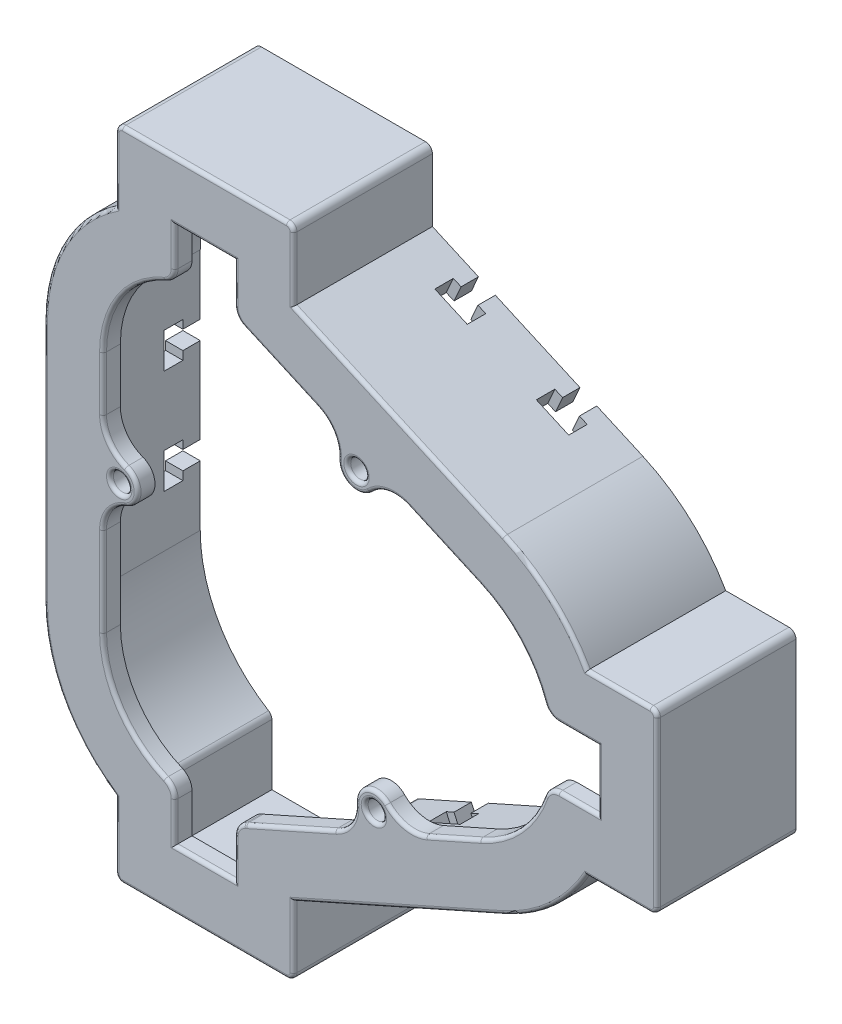
SolidWorks part; units mm, degrees
ref_plane "Front Plane" through (0, 0, 0) normal (0, 0, 1) x (1, 0, 0)
ref_plane "Top Plane" through (0, 0, 0) normal (0, 1, 0) x (1, 0, 0)
ref_plane "Right Plane" through (0, 0, 0) normal (1, 0, 0) x (0, 0, -1)
sketch "Sketch1" plane through (0, 0, -80.01) normal (0, 0, -1) x (-1, 0, 0)
  line L0 (14.1705, 137.7093) -> (22.108, 137.7093) construction
  line L1 (-128.3273, 40.8549) -> (-128.3273, 32.9174) construction
  line L2 (14.1705, -63.937) -> (22.108, -63.937) construction
  line L3 (55.2868, -7.5638) -> (55.2868, 81.3362)
  line L4 (29.093, 120.8247) -> (29.093, 135.1693)
  line L5 (29.093, 135.1693) -> (22.108, 135.1693)
  line L6 (14.1705, 135.1693) -> (22.108, 135.1693)
  line L7 (14.1705, 135.1693) -> (7.1855, 135.1693)
  line L8 (7.1855, 135.1693) -> (7.1855, 120.8247)
  line L9 (3.0278, 115.2711) -> (-82.5915, 77.144)
  line L10 (-111.5749, 47.8399) -> (-125.7873, 47.8399)
  line L11 (-125.7873, 47.8399) -> (-125.7873, 40.8549)
  line L12 (-125.7873, 40.8549) -> (-125.7873, 32.9174)
  line L13 (-125.7873, 32.9174) -> (-125.7873, 25.9324)
  line L14 (-125.7873, 25.9324) -> (-111.5749, 25.9324)
  line L15 (-82.5915, -3.3716) -> (3.0278, -41.4987)
  line L16 (7.1855, -47.0524) -> (7.1855, -61.397)
  line L17 (7.1855, -61.397) -> (14.1705, -61.397)
  line L18 (14.1705, -61.397) -> (22.108, -61.397)
  line L19 (22.108, -61.397) -> (29.093, -61.397)
  line L20 (29.093, -61.397) -> (29.093, -47.0524)
  line L21 (57.8268, -7.5638) -> (57.8268, 81.3362)
  line L22 (31.633, 120.8247) -> (31.633, 137.7093)
  line L23 (31.633, 137.7093) -> (22.108, 137.7093)
  line L24 (22.108, 137.7093) -> (22.108, 117.6323)
  line L25 (14.1705, 117.6323) -> (14.1705, 137.7093)
  line L26 (14.1705, 137.7093) -> (4.6455, 137.7093)
  line L27 (4.6455, 137.7093) -> (4.6455, 120.8247)
  line L28 (1.9945, 117.5914) -> (-83.6248, 79.4643)
  line L29 (-111.5749, 50.3799) -> (-128.3273, 50.3799)
  line L30 (-128.3273, 50.3799) -> (-128.3273, 40.8549)
  line L31 (-128.3273, 40.8549) -> (-106.0032, 40.8549)
  line L32 (-106.0032, 32.9174) -> (-128.3273, 32.9174)
  line L33 (-128.3273, 32.9174) -> (-128.3273, 23.3924)
  line L34 (-128.3273, 23.3924) -> (-111.5749, 23.3924)
  line L35 (-83.6248, -5.692) -> (1.9945, -43.8191)
  line L36 (4.6455, -47.0524) -> (4.6455, -63.937)
  line L37 (4.6455, -63.937) -> (14.1705, -63.937)
  line L38 (14.1705, -63.937) -> (14.1705, -43.86)
  line L39 (22.108, -43.86) -> (22.108, -63.937)
  line L40 (22.108, -63.937) -> (31.633, -63.937)
  line L41 (31.633, -63.937) -> (31.633, -47.0524)
  line L42 (57.8268, -7.5638) -> (57.8268, 81.3362) construction
  line L43 (31.633, 120.8247) -> (31.633, 137.7093) construction
  line L44 (31.633, 137.7093) -> (22.108, 137.7093) construction
  line L47 (14.1705, 137.7093) -> (4.6455, 137.7093) construction
  line L48 (4.6455, 137.7093) -> (4.6455, 120.8247) construction
  line L49 (1.9945, 117.5914) -> (-83.6248, 79.4643) construction
  line L50 (-111.5749, 50.3799) -> (-128.3273, 50.3799) construction
  line L51 (-128.3273, 50.3799) -> (-128.3273, 40.8549) construction
  line L54 (-128.3273, 32.9174) -> (-128.3273, 23.3924) construction
  line L55 (-128.3273, 23.3924) -> (-111.5749, 23.3924) construction
  line L56 (-83.6248, -5.692) -> (1.9945, -43.8191) construction
  line L57 (4.6455, -47.0524) -> (4.6455, -63.937) construction
  line L58 (4.6455, -63.937) -> (14.1705, -63.937) construction
  line L61 (22.108, -63.937) -> (31.633, -63.937) construction
  line L62 (31.633, -63.937) -> (31.633, -47.0524) construction
  line L63 (76.8768, -7.5638) -> (76.8768, 81.3362)
  line L64 (50.683, 130.234) -> (50.683, 156.7593)
  line L65 (50.683, 156.7593) -> (22.108, 156.7593)
  line L66 (14.1705, 156.7593) -> (22.108, 156.7593)
  line L67 (14.1705, 156.7593) -> (-14.4045, 156.7593)
  line L68 (-14.4045, 156.7593) -> (-14.4045, 131.1423)
  line L69 (-14.4045, 131.1423) -> (-91.3743, 96.8669)
  line L70 (-121.6907, 69.4299) -> (-147.3773, 69.4299)
  line L71 (-147.3773, 69.4299) -> (-147.3773, 40.8549)
  line L72 (-147.3773, 40.8549) -> (-147.3773, 32.9174)
  line L73 (-147.3773, 32.9174) -> (-147.3773, 4.3424)
  line L74 (-147.3773, 4.3424) -> (-121.6907, 4.3424)
  line L75 (-91.3743, -23.0945) -> (-14.4045, -57.3699)
  line L76 (-14.4045, -57.3699) -> (-14.4045, -82.987)
  line L77 (-14.4045, -82.987) -> (14.1705, -82.987)
  line L78 (14.1705, -82.987) -> (22.108, -82.987)
  line L79 (22.108, -82.987) -> (50.683, -82.987)
  line L80 (50.683, -82.987) -> (50.683, -56.4617)
  line L81 (70.5268, -7.5638) -> (70.5268, 81.3362)
  line L82 (44.333, 126.7051) -> (44.333, 150.4093)
  line L83 (44.333, 150.4093) -> (22.108, 150.4093)
  line L84 (14.1705, 150.4093) -> (22.108, 150.4093)
  line L85 (14.1705, 150.4093) -> (-8.0545, 150.4093)
  line L86 (-8.0545, 150.4093) -> (-8.0545, 127.0188)
  line L87 (-8.0545, 127.0188) -> (-88.7911, 91.066)
  line L88 (-117.8756, 63.0799) -> (-141.0273, 63.0799)
  line L89 (-141.0273, 63.0799) -> (-141.0273, 40.8549)
  line L90 (-141.0273, 40.8549) -> (-141.0273, 32.9174)
  line L91 (-141.0273, 32.9174) -> (-141.0273, 10.6924)
  line L92 (-141.0273, 10.6924) -> (-117.8756, 10.6924)
  line L93 (-88.7911, -17.2937) -> (-8.0545, -53.2465)
  line L94 (-8.0545, -53.2465) -> (-8.0545, -76.637)
  line L95 (-8.0545, -76.637) -> (14.1705, -76.637)
  line L96 (14.1705, -76.637) -> (22.108, -76.637)
  line L97 (22.108, -76.637) -> (44.333, -76.637)
  line L98 (44.333, -76.637) -> (44.333, -52.9327)
  circle A0 centre (18.1393, 81.3362) radius 19.05 construction
  circle A1 centre (18.1393, -7.5638) radius 47.625 construction
  circle A2 centre (-58.3701, 37.7264) radius 19.05 construction
  circle A3 centre (18.1393, 81.3362) radius 19.05 construction
  circle A4 centre (18.1393, -7.5638) radius 47.625 construction
  circle A5 centre (-58.3701, 37.7264) radius 19.05 construction
  arc A6 (-63.9876, 68.0881) -> (-52.7526, 7.3647) centre (-58.3701, 37.7264) ccw construction
  arc A7 (-63.9876, 68.0881) -> (-52.7526, 7.3647) centre (-58.3701, 37.7264) ccw construction
  arc A8 (-52.5707, 6.3814) -> (-64.1696, 69.0714) centre (-58.3701, 37.7264) ccw construction
  arc A9 (-52.5707, 6.3814) -> (-64.1696, 69.0714) centre (-58.3701, 37.7264) ccw construction
  circle A10 centre (18.1393, 81.3362) radius 36.5125 construction
  circle A11 centre (18.1393, 81.3362) radius 36.5125 construction
  circle A12 centre (49.3813, 43.2476) radius 3.3782
  circle A13 centre (-43.805, -14.1791) radius 3.3782
  circle A14 centre (-37.4305, 90.7903) radius 3.3782
  arc A15 (33.5733, -44.1273) -> (57.8268, -7.5638) centre (18.1393, -7.5638) ccw
  arc A16 (57.8268, 81.3362) -> (33.5733, 117.8997) centre (18.1393, 81.3362) ccw
  arc A17 (31.633, 120.8247) -> (33.5733, 117.8997) centre (34.808, 120.8247) ccw
  arc A18 (14.1705, 117.6323) -> (22.108, 117.6323) centre (18.1393, 81.3362) ccw
  arc A19 (2.7053, 117.8997) -> (4.6455, 120.8247) centre (1.4705, 120.8247) ccw
  arc A20 (2.7053, 117.8997) -> (1.9945, 117.5914) centre (18.1393, 81.3362) ccw
  arc A21 (-83.6248, 79.4643) -> (-108.5831, 52.4919) centre (-64.6643, 36.8862) ccw
  arc A22 (-111.5749, 50.3799) -> (-108.5831, 52.4919) centre (-111.5749, 53.5549) ccw
  arc A23 (-106.0032, 32.9174) -> (-106.0032, 40.8549) centre (-64.6643, 36.8862) ccw
  arc A24 (-108.5831, 21.2805) -> (-111.5749, 23.3924) centre (-111.5749, 20.2174) ccw
  arc A25 (-108.5831, 21.2805) -> (-83.6248, -5.692) centre (-64.6643, 36.8862) ccw
  arc A26 (1.9945, -43.8191) -> (2.7053, -44.1273) centre (18.1393, -7.5638) ccw
  arc A27 (4.6455, -47.0524) -> (2.7053, -44.1273) centre (1.4705, -47.0524) ccw
  arc A28 (22.108, -43.86) -> (14.1705, -43.86) centre (18.1393, -7.5638) ccw
  arc A29 (33.5733, -44.1273) -> (31.633, -47.0524) centre (34.808, -47.0524) ccw
  arc A30 (33.5733, -44.1273) -> (57.8268, -7.5638) centre (18.1393, -7.5638) ccw construction
  arc A31 (57.8268, 81.3362) -> (33.5733, 117.8997) centre (18.1393, 81.3362) ccw construction
  arc A32 (31.633, 120.8247) -> (33.5733, 117.8997) centre (34.808, 120.8247) ccw construction
  arc A34 (2.7053, 117.8997) -> (4.6455, 120.8247) centre (1.4705, 120.8247) ccw construction
  arc A35 (2.7053, 117.8997) -> (1.9945, 117.5914) centre (18.1393, 81.3362) ccw construction
  arc A36 (-83.6248, 79.4643) -> (-108.5831, 52.4919) centre (-64.6643, 36.8862) ccw construction
  arc A37 (-111.5749, 50.3799) -> (-108.5831, 52.4919) centre (-111.5749, 53.5549) ccw construction
  arc A39 (-108.5831, 21.2805) -> (-111.5749, 23.3924) centre (-111.5749, 20.2174) ccw construction
  arc A40 (-108.5831, 21.2805) -> (-83.6248, -5.692) centre (-64.6643, 36.8862) ccw construction
  arc A41 (1.9945, -43.8191) -> (2.7053, -44.1273) centre (18.1393, -7.5638) ccw construction
  arc A42 (4.6455, -47.0524) -> (2.7053, -44.1273) centre (1.4705, -47.0524) ccw construction
  arc A44 (33.5733, -44.1273) -> (31.633, -47.0524) centre (34.808, -47.0524) ccw construction
  arc A45 (-23.9136, 44.8884) -> (-23.2414, 39.853) centre (-64.6643, 36.8862) ccw construction
  arc A46 (-23.9136, 44.8884) -> (-23.2414, 39.853) centre (-64.6643, 36.8862) ccw construction
  circle A47 centre (-43.805, -14.1791) radius 6.7564
  circle A48 centre (49.3813, 43.2476) radius 6.7564
  circle A49 centre (-37.4305, 90.7903) radius 6.7564
  arc A50 (32.5855, -41.7872) -> (55.2868, -7.5638) centre (18.1393, -7.5638) ccw
  arc A51 (55.2868, 81.3362) -> (32.5855, 115.5596) centre (18.1393, 81.3362) ccw
  arc A52 (29.093, 120.8247) -> (32.5855, 115.5596) centre (34.808, 120.8247) ccw
  arc A53 (3.693, 115.5596) -> (7.1855, 120.8247) centre (1.4705, 120.8247) ccw
  arc A54 (3.693, 115.5596) -> (3.0278, 115.2711) centre (18.1393, 81.3362) ccw
  arc A55 (-82.5915, 77.144) -> (-106.1897, 51.6414) centre (-64.6643, 36.8862) ccw
  arc A56 (-111.5749, 47.8399) -> (-106.1897, 51.6414) centre (-111.5749, 53.5549) ccw
  arc A57 (-106.1897, 22.1309) -> (-111.5749, 25.9324) centre (-111.5749, 20.2174) ccw
  arc A58 (-106.1897, 22.1309) -> (-82.5915, -3.3716) centre (-64.6643, 36.8862) ccw
  arc A59 (3.0278, -41.4987) -> (3.693, -41.7872) centre (18.1393, -7.5638) ccw
  arc A60 (7.1855, -47.0524) -> (3.693, -41.7872) centre (1.4705, -47.0524) ccw
  arc A61 (32.5855, -41.7872) -> (29.093, -47.0524) centre (34.808, -47.0524) ccw
  arc A62 (50.683, -56.4617) -> (76.8768, -7.5638) centre (18.1393, -7.5638) ccw
  arc A63 (76.8768, 81.3362) -> (50.683, 130.234) centre (18.1393, 81.3362) ccw
  arc A64 (50.683, 130.234) -> (50.683, 130.234) centre (50.683, 130.234) ccw
  arc A65 (-14.4045, 131.1423) -> (-14.4045, 131.1423) centre (-14.4045, 131.1423) ccw
  arc A66 (-14.4045, 131.1423) -> (-14.4045, 131.1423) centre (-14.4045, 131.1423) cw
  arc A67 (-91.3743, 96.8669) -> (-121.6907, 69.4299) centre (-64.6643, 36.8862) ccw
  arc A68 (-121.6907, 69.4299) -> (-121.6907, 69.4299) centre (-121.6907, 69.4299) ccw
  arc A69 (-121.6907, 4.3424) -> (-121.6907, 4.3424) centre (-121.6907, 4.3424) ccw
  arc A70 (-121.6907, 4.3424) -> (-91.3743, -23.0945) centre (-64.6643, 36.8862) ccw
  arc A71 (-14.4045, -57.3699) -> (-14.4045, -57.3699) centre (-14.4045, -57.3699) cw
  arc A72 (-14.4045, -57.3699) -> (-14.4045, -57.3699) centre (-14.4045, -57.3699) ccw
  arc A73 (50.683, -56.4617) -> (50.683, -56.4617) centre (50.683, -56.4617) ccw
  arc A74 (44.333, -52.9327) -> (70.5268, -7.5638) centre (18.1393, -7.5638) ccw
  arc A75 (70.5268, 81.3362) -> (44.333, 126.7051) centre (18.1393, 81.3362) ccw
  arc A76 (44.333, 126.7051) -> (44.333, 126.7051) centre (44.333, 126.7051) ccw
  arc A77 (-8.0545, 127.0188) -> (-8.0545, 127.0188) centre (-8.0545, 127.0188) ccw
  arc A78 (-8.0545, 127.0188) -> (-8.0545, 127.0188) centre (-8.0545, 127.0188) cw
  arc A79 (-88.7911, 91.066) -> (-117.8756, 63.0799) centre (-64.6643, 36.8862) ccw
  arc A80 (-117.8756, 63.0799) -> (-117.8756, 63.0799) centre (-117.8756, 63.0799) ccw
  arc A81 (-117.8756, 10.6924) -> (-117.8756, 10.6924) centre (-117.8756, 10.6924) ccw
  arc A82 (-117.8756, 10.6924) -> (-88.7911, -17.2937) centre (-64.6643, 36.8862) ccw
  arc A83 (-8.0545, -53.2465) -> (-8.0545, -53.2465) centre (-8.0545, -53.2465) cw
  arc A84 (-8.0545, -53.2465) -> (-8.0545, -53.2465) centre (-8.0545, -53.2465) ccw
  arc A85 (44.333, -52.9327) -> (44.333, -52.9327) centre (44.333, -52.9327) ccw
  point P68 (-40.8151, 98.5279)
  arc M83 (33.5733, -44.1273) -> (57.8268, -7.5638) centre (18.1393, -7.5638) ccw
  line M84 (57.8268, -7.5638) -> (57.8268, 81.3362)
  arc M85 (57.8268, 81.3362) -> (33.5733, 117.8997) centre (18.1393, 81.3362) ccw
  arc M86 (33.5733, 117.8997) -> (31.633, 120.8247) centre (34.808, 120.8247) cw
  line M87 (31.633, 120.8247) -> (31.633, 137.7093)
  line M88 (31.633, 137.7093) -> (22.108, 137.7093)
  line M89 (22.108, 137.7093) -> (22.108, 117.6323)
  line M91 (14.1705, 117.6323) -> (14.1705, 137.7093)
  line M92 (14.1705, 137.7093) -> (4.6455, 137.7093)
  line M93 (4.6455, 137.7093) -> (4.6455, 120.8247)
  arc M94 (4.6455, 120.8247) -> (2.7053, 117.8997) centre (1.4705, 120.8247) cw
  arc M95 (2.7053, 117.8997) -> (1.9945, 117.5914) centre (18.1393, 81.3362) ccw
  line M96 (1.9945, 117.5914) -> (-83.6248, 79.4643)
  arc M97 (-83.6248, 79.4643) -> (-108.5831, 52.4919) centre (-64.6643, 36.8862) ccw
  arc M98 (-108.5831, 52.4919) -> (-111.5749, 50.3799) centre (-111.5749, 53.5549) cw
  line M99 (-111.5749, 50.3799) -> (-128.3273, 50.3799)
  line M100 (-128.3273, 50.3799) -> (-128.3273, 40.8549)
  line M101 (-128.3273, 40.8549) -> (-106.0032, 40.8549)
  line M103 (-106.0032, 32.9174) -> (-128.3273, 32.9174)
  line M104 (-128.3273, 32.9174) -> (-128.3273, 23.3924)
  line M105 (-128.3273, 23.3924) -> (-111.5749, 23.3924)
  arc M106 (-111.5749, 23.3924) -> (-108.5831, 21.2805) centre (-111.5749, 20.2174) cw
  arc M107 (-108.5831, 21.2805) -> (-83.6248, -5.692) centre (-64.6643, 36.8862) ccw
  line M108 (-83.6248, -5.692) -> (1.9945, -43.8191)
  arc M109 (1.9945, -43.8191) -> (2.7053, -44.1273) centre (18.1393, -7.5638) ccw
  arc M110 (2.7053, -44.1273) -> (4.6455, -47.0524) centre (1.4705, -47.0524) cw
  line M111 (4.6455, -47.0524) -> (4.6455, -63.937)
  line M112 (4.6455, -63.937) -> (14.1705, -63.937)
  line M113 (14.1705, -63.937) -> (14.1705, -43.86)
  line M115 (22.108, -43.86) -> (22.108, -63.937)
  line M116 (22.108, -63.937) -> (31.633, -63.937)
  line M117 (31.633, -63.937) -> (31.633, -47.0524)
  arc M118 (31.633, -47.0524) -> (33.5733, -44.1273) centre (34.808, -47.0524) cw
  dimension "D2" = 6.7564
  dimension "D3" = 8.4455
  dimension "D4" = 8.4455
  dimension "D5" = 8.4455
  dimension "D6" = 3.3782
  dimension "D1" = 0
  dimension "D7" = 2.54
  dimension "D8" = 19.05
  dimension "D9" = 12.7
extrude "Boss-Extrude1" add sketch "Sketch1" along normal blind 6.35 contours L3 A48 A12 | L9 A49 A14 | L15 A47 A13 | L92 A82 L93 L94 L95 L96 L97 L98 A74 L81 A75 L82 L83 L84 L85 L86 L87 A79 L88 L89 L90 L91 L18 L12 L6 M113 M112 M111 M110 M109 M108 M107 M106 M105 M104 M103 M101 M100 M99 M98 M97 M96 M95 M94 M93 M92 M91 M89 M88 M87 | L16 A60 A59 L15 A47 A58 A57 L14 L13 L17 M103 M104 M105 M106 M107 M108 M109 M110 M111 M112 M113 | A50 A61 L20 L19 L5 L4 A52 A51 L3 A48 M115 M116 M117 M118 M83 M84 M85 M86 M87 M88 M89 | L10 A56 A55 L9 A49 A54 A53 L8 L7 L11 M91 M92 M93 M94 M95 M96 M97 M98 M99 M100 M101 | L74 A70 L75 L76 L77 L78 L79 L80 A62 L63 A63 L64 L65 L66 L67 L68 L69 A67 L70 L71 L72 L73 A82 L92 L91 L90 L89 L88 A79 L87 L86 L85 L84 L83 L82 A75 L81 A74 L98 L97 L96 L95 L94 L93 | L3 A48 | L9 A49 | L15 A47 region at (-57.3347, 16.2007, -80.01) region at (-42.8101, 43.2476, -80.01) region at (-55.6291, 43.2476, -80.01) region at (-12.4476, -62.667, -80.01) region at (-10.678, 136.8923, -80.01) region at (46.3466, -19.8865, -80.01) region at (46.1297, -19.3994, -80.01) region at (32.5874, 95.2231, -80.01) region at (39.972, 96.4976, -80.01) region at (-67.0221, -33.7495, -80.01) region at (-60.8207, -32.2059, -80.01)
extrude "Boss-Extrude2" add sketch "Sketch1<3>" along normal blind 50.8 contours L74 A70 L75 L76 L77 L78 L79 L80 A62 L63 A63 L64 L65 L66 L67 L68 L69 A67 L70 L71 L72 L73 A82 L92 L91 L90 L89 L88 A79 L87 L86 L85 L84 L83 L82 A75 L81 A74 L98 L97 L96 L95 L94 L93 region at (-67.0221, -33.7495, -80.01)
sketch "Sketch1<3>" plane through (0, 0, -80.01) normal (0, 0, -1) x (-1, 0, 0) same geometry as "Sketch1"
sketch "Sketch2" plane through (-76.8768, 0, 0) normal (-1, 0, 0) x (0, 0, 1)
  line L0 (-80.01, 36.8862) -> (-130.81, 36.8862) construction
  line L1 (-130.81, 395.458) -> (-130.81, 402.2144)
  line L2 (-80.01, -7.5638) -> (-80.01, 81.3362) construction
  line L3 (-130.81, -7.5638) -> (-130.81, 81.3362) construction
  line L4 (-130.81, 52.558) -> (-124.46, 52.558)
  line L5 (-124.46, 52.558) -> (-124.46, 49.4592)
  line L6 (-124.46, 49.4592) -> (-117.602, 49.4592)
  line L7 (-117.602, 49.4592) -> (-117.602, 62.4132)
  line L8 (-117.602, 55.9362) -> (-130.81, 55.9362) construction
  line L9 (-124.46, 62.4132) -> (-117.602, 62.4132)
  line L10 (-130.81, 59.3144) -> (-124.46, 59.3144)
  line L11 (-124.46, 59.3144) -> (-124.46, 62.4132)
  line L12 (-130.81, 14.458) -> (-124.46, 14.458)
  line L13 (-124.46, 14.458) -> (-124.46, 11.3592)
  line L14 (-124.46, 11.3592) -> (-117.602, 11.3592)
  line L15 (-117.602, 24.3132) -> (-117.602, 11.3592)
  line L16 (-124.46, 24.3132) -> (-117.602, 24.3132)
  line L17 (-124.46, 21.2144) -> (-124.46, 24.3132)
  line L18 (-130.81, 21.2144) -> (-124.46, 21.2144)
  line L19 (-130.81, 14.458) -> (-130.81, 21.2144)
  line L20 (-130.81, 52.558) -> (-130.81, 59.3144)
  line L21 (-130.81, 402.2144) -> (-124.46, 402.2144)
  line L22 (-124.46, 402.2144) -> (-124.46, 405.3132)
  line L23 (-124.46, 405.3132) -> (-117.602, 405.3132)
  line L24 (-117.602, 405.3132) -> (-117.602, 392.3592)
  line L25 (-124.46, 392.3592) -> (-117.602, 392.3592)
  line L26 (-124.46, 395.458) -> (-124.46, 392.3592)
  line L27 (-130.81, 395.458) -> (-124.46, 395.458)
  line L28 (-130.81, 433.558) -> (-130.81, 440.3144)
  line L29 (-130.81, 440.3144) -> (-124.46, 440.3144)
  line L30 (-124.46, 440.3144) -> (-124.46, 443.4132)
  line L31 (-124.46, 443.4132) -> (-117.602, 443.4132)
  line L32 (-117.602, 430.4592) -> (-117.602, 443.4132)
  line L33 (-124.46, 430.4592) -> (-117.602, 430.4592)
  line L34 (-124.46, 433.558) -> (-124.46, 430.4592)
  line L35 (-130.81, 433.558) -> (-124.46, 433.558)
  dimension "D1" = 6.858
  dimension "D2" = 6.7564
  dimension "D3" = 6.35
  dimension "D4" = 19.05
  dimension "D6" = 6.477
  dimension "D5" = 2
sketch "Sketch3" plane through (51.1185, 114.7931, 0) normal (0.4068, 0.9135, 0) x (0.9135, -0.4068, 0)
  line L0 (1.9385, 130.81) -> (1.9385, 80.01) construction
  line L1 (-40.1897, 130.81) -> (44.0668, 130.81) construction
  line L2 (-40.1897, 80.01) -> (44.0668, 80.01) construction
  line L3 (22.2585, 130.81) -> (22.2585, 117.7036) construction
  line L4 (18.8803, 130.81) -> (18.8803, 124.46)
  line L5 (18.8803, 124.46) -> (15.7815, 124.46)
  line L6 (15.7815, 124.46) -> (15.7815, 117.7036)
  line L7 (15.7815, 117.7036) -> (28.7355, 117.7036)
  line L8 (28.7355, 124.46) -> (28.7355, 117.7036)
  line L9 (25.6367, 124.46) -> (28.7355, 124.46)
  line L10 (25.6367, 130.81) -> (25.6367, 124.46)
  line L11 (-18.3815, 130.81) -> (-18.3815, 117.7036) construction
  line L12 (-21.7597, 130.81) -> (-21.7597, 124.46)
  line L13 (-15.0033, 130.81) -> (-15.0033, 124.46)
  line L14 (-21.7597, 124.46) -> (-24.8585, 124.46)
  line L15 (-24.8585, 124.46) -> (-24.8585, 117.7036)
  line L16 (-15.0033, 124.46) -> (-11.9045, 124.46)
  line L17 (-11.9045, 124.46) -> (-11.9045, 117.7036)
  line L18 (-11.9045, 117.7036) -> (-24.8585, 117.7036)
  line L19 (-21.7597, 130.81) -> (-15.0033, 130.81)
  line L20 (18.8803, 130.81) -> (25.6367, 130.81)
  dimension "D1" = 3.3782
  dimension "D2" = 6.7564
  dimension "D3" = 6.35
  dimension "D4" = 6.477
  dimension "D5" = 20.32
extrude "Cut-Extrude1" cut sketch "Sketch3" against normal blind 18.542
ref_plane "Plane4" through (0, 36.8862, 0) normal (0, 1, 0) x (1, 0, 0)
mirror "Mirror1" about plane through (0, 36.8862, 0) normal (0, 1, 0) of "Cut-Extrude1"
extrude "Cut-Extrude2" cut sketch "Sketch2" against normal blind 18.542
fillet "Fillet1" radius 12.7 6 edges at (49.2059, -18.2386, -83.185) (43.2089, -20.9091, -83.185) (-55.2868, 46.53, -83.185) (-55.2868, 39.9652, -83.185) (42.8316, 94.8495, -83.185) (36.8339, 97.5203, -83.185)
fillet "Fillet2" radius 2.54 16 edges at (141.0273, 63.0799, -108.585) (141.0273, 10.6924, -108.585) (8.0545, 150.4093, -108.585) (-44.333, 150.4093, -108.585) (8.0545, 127.0188, -108.585) (-44.333, 126.7051, -108.585) (8.0545, -53.2465, -108.585) (-44.333, -52.9327, -108.585) (14.4045, -82.987, -105.41) (-50.683, -82.987, -105.41) (-50.683, 156.7593, -105.41) (14.4045, 156.7593, -105.41) (147.3773, 69.4299, -105.41) (147.3773, 4.3424, -105.41) (117.8756, 10.6924, -108.585) (117.8756, 63.0799, -108.585)
fillet "Fillet3" radius 1.27 61 edges at (-49.9391, -82.243, -80.01) (-50.683, -68.4543, -80.01) (-69.9159, -35.2997, -80.01) (-76.8768, 36.8862, -80.01) (-69.9159, 109.072, -80.01) (-50.683, 142.2267, -80.01) (-49.9391, 156.0154, -80.01) (-18.1393, 156.7593, -80.01) (13.6605, 156.0154, -80.01) (14.4045, 142.6808, -80.01) (52.8894, 114.0046, -80.01) (108.7227, 85.5684, -80.01) (133.264, 69.4299, -80.01) (146.6333, 68.686, -80.01) (147.3773, 36.8862, -80.01) (146.6333, 5.0864, -80.01) (133.264, 4.3424, -80.01) (108.7227, -11.7961, -80.01) (52.8894, -40.2322, -80.01) (14.4045, -68.9084, -80.01) (13.6605, -82.243, -80.01) (-18.1393, -82.987, -80.01) (34.0523, 90.7903, -80.01) (-52.7595, 43.2476, -80.01) (40.4268, -14.1791, -80.01) (118.6811, 47.8399, -80.01) (108.279, 48.886, -80.01) (97.0101, 66.8166, -80.01) (69.5395, 82.9562, -80.01) (48.9466, 89.6427, -80.01) (34.682, 84.6182, -80.01) (28.873, 98.5817, -80.01) (10.0751, 109.4362, -80.01) (-3.3597, 115.417, -80.01) (-6.233, 117.6657, -80.01) (-7.1855, 127.997, -80.01) (-18.1393, 135.1693, -80.01) (-29.093, 127.997, -80.01) (-30.0455, 117.6657, -80.01) (-49.0955, 101.8702, -80.01) (-55.2868, 71.4076, -80.01) (-53.0179, 54.2346, -80.01) (-42.6249, 43.2476, -80.01) (-53.0179, 32.2606, -80.01) (-55.2868, 8.7262, -80.01) (-49.0955, -28.0979, -80.01) (-30.0455, -43.8933, -80.01) (-29.093, -54.2247, -80.01) (-18.1393, -61.397, -80.01) (-7.1855, -54.2247, -80.01) (-6.233, -43.8933, -80.01) (-3.3597, -41.6446, -80.01) (13.2624, -34.2446, -80.01) (35.2476, -21.9706, -80.01) (41.0565, -8.007, -80.01) (55.3212, -13.0317, -80.01) (72.7268, -7.7645, -80.01) (97.0101, 6.9558, -80.01) (108.279, 24.8863, -80.01) (118.6811, 25.9324, -80.01) (125.7873, 36.8862, -80.01)
equation "\"D4@Sketch1\"=\"D3@Sketch1\""
equation "\"D5@Sketch1\"=\"D3@Sketch1\""
